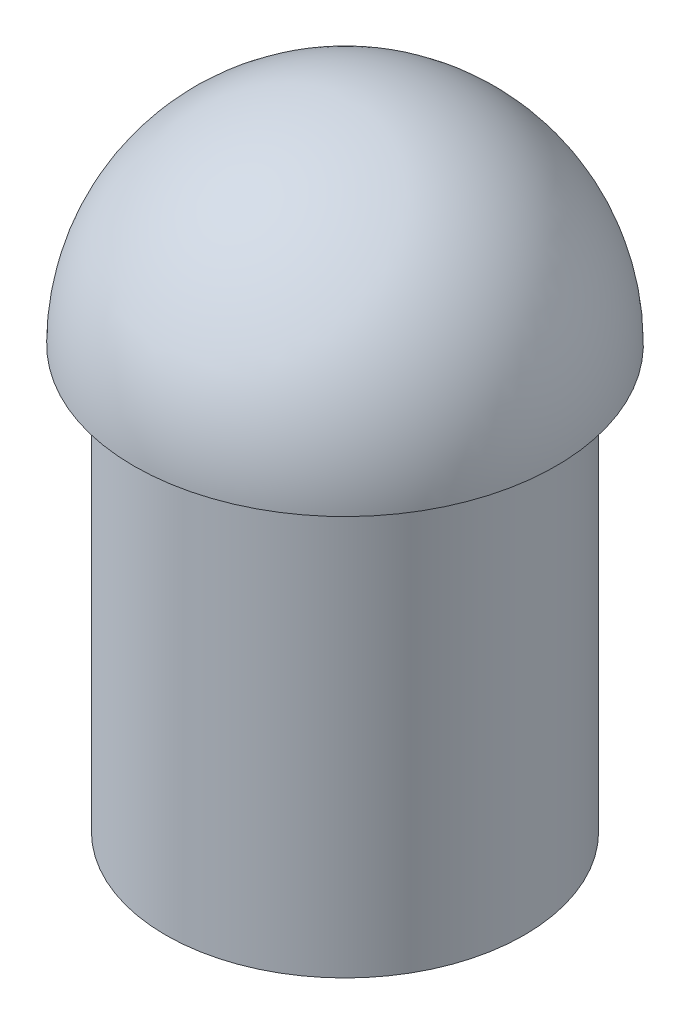
SolidWorks part; units mm, degrees
ref_plane "Front Plane" through (0, 0, 0) normal (0, 0, 1) x (1, 0, 0)
ref_plane "Top Plane" through (0, 0, 0) normal (0, 1, 0) x (1, 0, 0)
ref_plane "Right Plane" through (0, 0, 0) normal (1, 0, 0) x (0, 0, -1)
sketch "Sketch1" plane through (0, 0, 0) normal (1, 0, 0) x (0, 0, -1)
  line L1 (0, 0) -> (2.5, 0)
  line L2 (0, 0) -> (0, 2.5)
  arc A1 (0, 2.5) -> (2.5, 0) centre (0, 0) cw
  dimension "D1" = 2.5
  dimension "D2" = 2.5
ref_axis "Axis1" through (0, 0, 0) along (0, 1, 0)
revolve "Revolve5" add sketch "Sketch1" angle 360 about axis through (0, 0, 0) along (0, 1, 0) region at (0, 1.061, -1.061)
sketch "Sketch3" plane through (0, 0, 0) normal (0, -1, 0) x (1, 0, 0)
  line L1 (-1.5026, -1.5026) -> (1.5026, -1.5026) construction
  line L2 (-1.5026, -1.5026) -> (-1.5026, 1.5026) construction
  line L3 (-1.5026, 1.5026) -> (1.5026, 1.5026) construction
  line L4 (1.5026, -1.5026) -> (1.5026, 1.5026) construction
  line L5 (-1.5026, -1.5026) -> (1.5026, 1.5026) construction
  line L6 (-1.5026, 1.5026) -> (1.5026, -1.5026) construction
  circle A0 centre (0, 0) radius 2.125
  point P0 (0, 0)
  dimension "D1" = 4.25
extrude "Boss-Extrude1" add sketch "Sketch3" along normal blind 5
sketch "Sketch4" plane through (0, -5, 0) normal (0, -1, 0) x (1, 0, 0)
  line L1 (-1.425, -1.425) -> (1.425, -1.425)
  line L2 (-1.425, -1.425) -> (-1.425, 1.425)
  line L3 (-1.425, 1.425) -> (1.425, 1.425)
  line L4 (1.425, -1.425) -> (1.425, 1.425)
  line L5 (-1.425, -1.425) -> (1.425, 1.425) construction
  line L6 (-1.425, 1.425) -> (1.425, -1.425) construction
  point P0 (0, 0)
  dimension "D1" = 2.85
extrude "Cut-Extrude1" cut sketch "Sketch4" against normal blind 2
